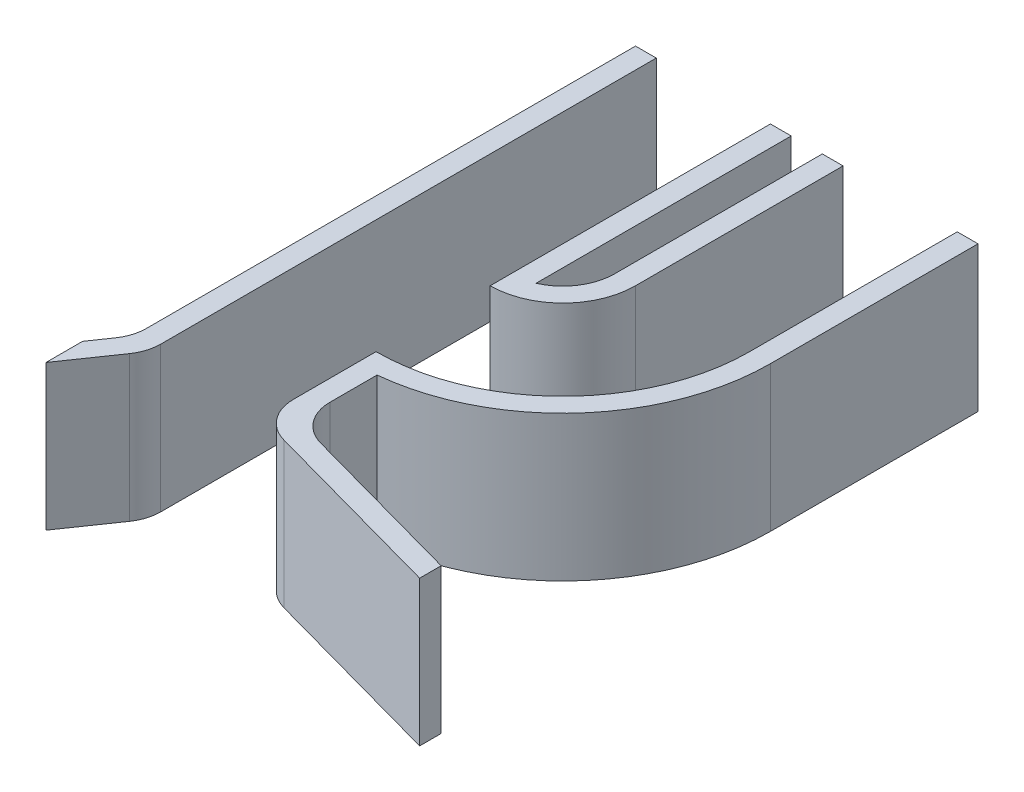
SolidWorks part; units mm, degrees
ref_plane "Front Plane" through (0, 0, 0) normal (0, 0, 1) x (1, 0, 0)
ref_plane "Top Plane" through (0, 0, 0) normal (0, 1, 0) x (1, 0, 0)
ref_plane "Right Plane" through (0, 0, 0) normal (1, 0, 0) x (0, 0, -1)
sketch "Sketch1" plane through (0, 0, 0) normal (0, 1, 0) x (1, 0, 0)
  line L0 (0, -55) -> (0, 55) construction
  line L1 (-47.5, -29) -> (-27.5, 0)
  line L2 (-27.5, 0) -> (-27.5, 245)
  line L3 (-27.5, 245) -> (-37.5, 245)
  line L6 (-37.5, 245) -> (-37.5, 3.1139)
  line L7 (-37.5, 3.1139) -> (-47.5, -11.3861)
  line L8 (-47.5, -11.3861) -> (-47.5, -29)
  line L9 (27.5, 0) -> (27.5, 55)
  line L10 (27.5, 55) -> (37.5, 55)
  line L11 (37.5, 55) -> (37.5, 7.6125)
  line L12 (37.5, 7.6125) -> (132.5, -18.6256)
  line L13 (132.5, -18.6256) -> (132.5, -29)
  line L14 (132.5, -29) -> (27.5, 0)
  line L15 (27.5, 245) -> (37.5, 245)
  line L16 (37.5, 245) -> (37.5, 120)
  line L17 (37.5, 120) -> (27.5, 120)
  line L18 (27.5, 120) -> (27.5, 245)
  line L19 (52.5, 145) -> (52.5, 245)
  line L20 (0, 134.0639) -> (0, -73.1656) construction
  line L21 (52.5, 245) -> (62.5, 245)
  line L22 (62.5, 245) -> (62.5, 145)
  line L23 (27.5, 110) -> (27.5, 120)
  line L24 (117.5, 145) -> (117.5, 245)
  line L25 (127.5, 145) -> (127.5, 245)
  line L26 (127.5, 245) -> (117.5, 245)
  line L27 (27.5, 55) -> (27.5, 45)
  line L28 (72.5, 145) -> (72.5, 245)
  line L29 (72.5, 245) -> (62.5, 245)
  line L30 (27.5, 100) -> (27.5, 110)
  line L31 (37.5, 55) -> (37.5, 55.5573)
  line L32 (27.5, 65) -> (27.5, 55)
  line L33 (37.5, 55) -> (27.5, 55)
  line L34 (107.5, 145) -> (107.5, 245)
  line L35 (107.5, 245) -> (117.5, 245)
  circle A0 centre (0, 0) radius 25 construction
  arc A1 (27.5, 55) -> (117.5, 145) centre (27.5, 145) ccw
  arc A2 (27.5, 45) -> (127.5, 145) centre (27.5, 145) ccw
  arc A3 (27.5, 110) -> (62.5, 145) centre (27.5, 145) ccw
  arc A4 (27.5, 120) -> (52.5, 145) centre (27.5, 145) ccw
  arc A5 (27.5, 100) -> (72.5, 145) centre (27.5, 145) ccw
  arc A6 (27.5, 65) -> (107.5, 145) centre (27.5, 145) ccw
  point P42 (27.5, 145)
  dimension "D1" = 50
  dimension "D15" = 10
  dimension "D17" = 100
  dimension "D18" = 90
  dimension "D8" = 35
  dimension "D9" = 25
  dimension "D19" = 45
  dimension "D20" = 80
  dimension "D2" = 10
  dimension "D3" = 274
  dimension "D4" = 10
  dimension "D5" = 10
  dimension "D6" = 10
  dimension "D7" = 10
  dimension "D10" = 55
  dimension "D11" = 180
  dimension "D12" = 55
  dimension "D13" = 10
  dimension "D14" = 100
  dimension "D16" = 10
extrude "Boss-Extrude1" add sketch "Sketch1" along normal blind 70 contours L11 A2 L25 L26 L24 A1 | L18 L17 L16 L15 | A2 L27 A1 L11 L10 L9 L14 L13 L12 | A4 L16 L17 L23 A3 L22 L21 L19 | A4 L17 L16 | L9 A2 L11 L10 | L14 L9 L10 L11 L12 L13 | A4 L19 L21 L22 A3 L23 | L27 A2 L25 L26 L24 A1 | L3 L6 L7 L8 L1 L2 region at (28.7875, 0, -22.5) region at (32.4575, 0, -50.0823) region at (39.6886, 0, -50.2506) region at (32.4861, 0, -182.8403) region at (35.0213, 0, -120.6214) region at (54.1538, 0, -173.0547)
fillet "Fillet1" radius 20 2 edges at (37.5, 35, -7.6125) (27.5, 35, 0)
fillet "Fillet2" radius 20 2 edges at (-37.5, 35, -3.1139) (-27.5, 35, 0)
ref_plane "Plane1" through (0, 35, 0) normal (0, 1, 0) x (1, 0, 0)
ref_plane "Plane2" through (0, 55, 0) normal (0, 1, 0) x (1, 0, 0)
ref_plane "Plane3" through (0, 0, -145) normal (0, 0, -1) x (-1, 0, 0)
ref_axis "Axis1" through (27.5, 70, -145) along (0, -1, 0)
